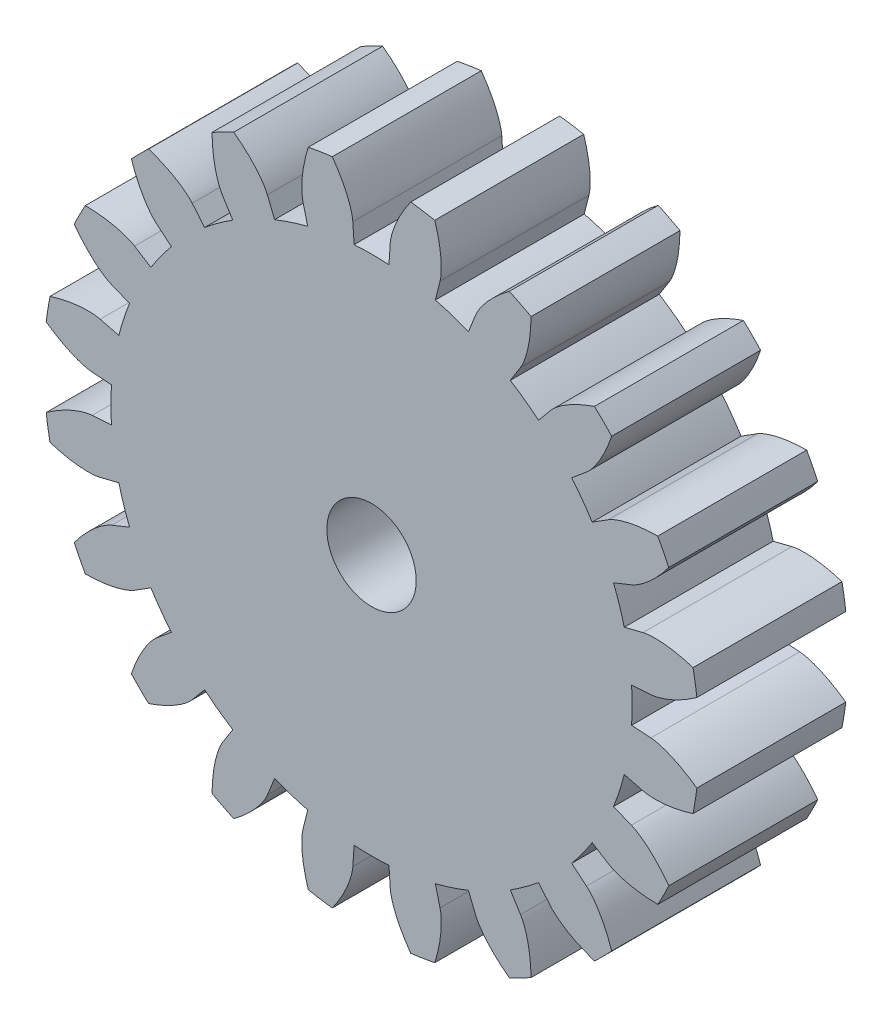
SolidWorks part; units mm, degrees
ref_plane "前视基准面" through (0, 0, 0) normal (0, 0, 1) x (1, 0, 0)
ref_plane "上视基准面" through (0, 0, 0) normal (0, 1, 0) x (1, 0, 0)
ref_plane "右视基准面" through (0, 0, 0) normal (1, 0, 0) x (0, 0, -1)
other "Configuration Table"
sketch "草图1" plane through (0, 0, 0) normal (0, 0, 1) x (1, 0, 0)
  line L0 (0, 0) -> (10, 0) construction
  line L1 (0, 0) -> (9.9692, 0.7846) construction
  line L2 (0, 0) -> (9.3759, 0.6279)
  line L3 (9.9692, 0.7846) -> (9.9692, -0.7846) construction
  line L4 (0, 0) -> (9.3759, -0.6279)
  circle A0 centre (0, 0) radius 11
  circle A1 centre (0, 0) radius 10 construction
  circle A2 centre (0, 0) radius 8.75
  circle A3 centre (0, 0) radius 9.3969 construction
  circle A4 centre (0, 0) radius 1.5
  spline S0 degree 4 poles (9.3759, 0.6279) (9.4116, 0.6303) (9.4826, 0.6384) (9.6794, 0.6787) (10.0428, 0.7996) (10.5707, 1.0588) (11.234, 1.5202) (11.9927, 2.2295) (12.7477, 3.1843) (13.4177, 4.3414) (13.9607, 5.6757) (14.3344, 7.0662) (14.5486, 8.4895) (14.616, 9.9981) (14.5044, 11.8649) (14.0866, 14.0589) (13.234, 16.5111) (11.8775, 19.0558) (10.17, 21.3779) (8.1655, 23.4475) (6.1953, 25.0195) (4.3812, 26.1876) (2.7992, 27.0391) (1.4966, 27.6465) (0.162, 28.1797) (-1.2002, 28.6385) (-2.9309, 29.1192) (-4.693, 29.4765) (-6.2962, 29.6882) (-7.73, 29.7923) (-8.5041, 29.8228) (-8.9819, 29.8324) (-9.3832, 29.8353) (-9.8079, 29.8331) (-10.1583, 29.8266) (-10.8253, 29.8047) (-11.3293, 29.7736) (-11.953, 29.7293) (-12.5015, 29.6752) (-13.0964, 29.6093) (-13.6567, 29.5329) (-14.0975, 29.4672) (-14.3768, 29.4201) (-14.5223, 29.3955) knots 0 0 0 0 0 0.002802 0.005604 0.015718 0.02996 0.048734 0.068727 0.096889 0.125051 0.153212 0.181374 0.209535 0.237696 0.271429 0.327752 0.384075 0.440398 0.496721 0.553044 0.609367 0.637529 0.66569 0.693852 0.722013 0.750174 0.778336 0.834659 0.86282 0.876901 0.890982 0.895509 0.900036 0.909091 0.920455 0.931818 0.943182 0.954545 0.965909 0.977273 0.988636 1 1 1 1 1 construction
  spline S1 degree 4 poles (9.3759, 0.6279) (9.4116, 0.6303) (9.4826, 0.6384) (9.6794, 0.6787) (10.0428, 0.7996) (10.5707, 1.0588) (11.234, 1.5202) (11.9927, 2.2295) (12.7477, 3.1843) (13.4177, 4.3414) (13.9607, 5.6757) (14.3344, 7.0662) (14.5486, 8.4895) (14.616, 9.9981) (14.5044, 11.8649) (14.0866, 14.0589) (13.234, 16.5111) (11.8775, 19.0558) (10.17, 21.3779) (8.1655, 23.4475) (6.1953, 25.0195) (4.3812, 26.1876) (2.7992, 27.0391) (1.4966, 27.6465) (0.162, 28.1797) (-1.2002, 28.6385) (-2.9309, 29.1192) (-4.693, 29.4765) (-6.2962, 29.6882) (-7.73, 29.7923) (-8.5041, 29.8228) (-8.9819, 29.8324) (-9.3832, 29.8353) (-9.6441, 29.834) (-9.8047, 29.8322) (-9.9096, 29.8304) knots 0 0 0 0 0 0.002802 0.005604 0.015718 0.02996 0.048734 0.068727 0.096889 0.125051 0.153212 0.181374 0.209535 0.237696 0.271429 0.327752 0.384075 0.440398 0.496721 0.553044 0.609367 0.637529 0.66569 0.693852 0.722013 0.750174 0.778336 0.834659 0.86282 0.876901 0.890982 0.895509 0.900036 0.909091 0.909091 0.909091 0.909091 0.909091
  spline S2 degree 4 poles (9.3759, -0.6279) (9.4116, -0.6303) (9.4826, -0.6384) (9.6794, -0.6787) (10.0428, -0.7996) (10.5707, -1.0588) (11.234, -1.5202) (11.9927, -2.2295) (12.7477, -3.1843) (13.4177, -4.3414) (13.9607, -5.6757) (14.3344, -7.0662) (14.5486, -8.4895) (14.616, -9.9981) (14.5044, -11.8649) (14.0866, -14.0589) (13.234, -16.5111) (11.8775, -19.0558) (10.17, -21.3779) (8.1655, -23.4475) (6.1953, -25.0195) (4.3812, -26.1876) (2.7992, -27.0391) (1.4966, -27.6465) (0.162, -28.1797) (-1.2002, -28.6385) (-2.9309, -29.1192) (-4.693, -29.4765) (-6.2962, -29.6882) (-7.73, -29.7923) (-8.5041, -29.8228) (-8.9819, -29.8324) (-9.3832, -29.8353) (-9.8079, -29.8331) (-10.1583, -29.8266) (-10.8253, -29.8047) (-11.3293, -29.7736) (-11.953, -29.7293) (-12.5015, -29.6752) (-13.0964, -29.6093) (-13.6567, -29.5329) (-14.0975, -29.4672) (-14.3768, -29.4201) (-14.5223, -29.3955) knots 0 0 0 0 0 0.002802 0.005604 0.015718 0.02996 0.048734 0.068727 0.096889 0.125051 0.153212 0.181374 0.209535 0.237696 0.271429 0.327752 0.384075 0.440398 0.496721 0.553044 0.609367 0.637529 0.66569 0.693852 0.722013 0.750174 0.778336 0.834659 0.86282 0.876901 0.890982 0.895509 0.900036 0.909091 0.920455 0.931818 0.943182 0.954545 0.965909 0.977273 0.988636 1 1 1 1 1 construction
  spline S3 degree 4 poles (9.3759, -0.6279) (9.4116, -0.6303) (9.4826, -0.6384) (9.6794, -0.6787) (10.0428, -0.7996) (10.5707, -1.0588) (11.234, -1.5202) (11.9927, -2.2295) (12.7477, -3.1843) (13.4177, -4.3414) (13.9607, -5.6757) (14.3344, -7.0662) (14.5486, -8.4895) (14.616, -9.9981) (14.5044, -11.8649) (14.0866, -14.0589) (13.234, -16.5111) (11.8775, -19.0558) (10.17, -21.3779) (8.1655, -23.4475) (6.1953, -25.0195) (4.3812, -26.1876) (2.7992, -27.0391) (1.4966, -27.6465) (0.162, -28.1797) (-1.2002, -28.6385) (-2.9309, -29.1192) (-4.693, -29.4765) (-6.2962, -29.6882) (-7.73, -29.7923) (-8.5041, -29.8228) (-8.9819, -29.8324) (-9.3832, -29.8353) (-9.6441, -29.834) (-9.8047, -29.8322) (-9.9096, -29.8304) knots 0 0 0 0 0 0.002802 0.005604 0.015718 0.02996 0.048734 0.068727 0.096889 0.125051 0.153212 0.181374 0.209535 0.237696 0.271429 0.327752 0.384075 0.440398 0.496721 0.553044 0.609367 0.637529 0.66569 0.693852 0.722013 0.750174 0.778336 0.834659 0.86282 0.876901 0.890982 0.895509 0.900036 0.909091 0.909091 0.909091 0.909091 0.909091
  point P15 (9.9692, 0)
  dimension "齿顶圆直径" = 22
  dimension "分度圆直径" = 20
  dimension "齿根圆直径" = 17.5
  dimension "基圆直径" = 18.7939
  dimension "内孔直径" = 3
  dimension "渐近线镜像线夹角" = 4.5
extrude "凸台-拉伸1" add sketch "草图1" along normal blind 5 contours A0 | A4
extrude "切除-拉伸1" cut sketch "草图1<3>" along normal through all contours A2 S3 A0 S1 region at (10.0281, 0, 0)
sketch "草图1<3>" plane through (0, 0, 0) normal (0, 0, 1) x (1, 0, 0) same geometry as "草图1"
pattern_circular "阵列(圆周)1" count 20 every 18 about axis through (0, 0, 5) along (0, 0, 1) of "切除-拉伸1"
equation "\"m\"= 1'模数"
equation "\"z\"= 20'齿数"
equation "\"a\"= 20度'压力角"
equation "\"d\"= \"m\" * \"z\"'分度圆直径"
equation "\"da\"= ( \"z\" + 2 ) * \"m\"'齿顶圆直径"
equation "\"df\"= ( \"z\" - 2.5 ) * \"m\"'齿根圆直径"
equation "\"s\"= 0.5 * PI * \"m\"'分度圆齿厚"
equation "\"r\"= 0.38 * \"m\"'齿根圆角"
equation "\"B\"= 0.3 * \"d\"'齿厚"
equation "\"db\"= \"m\" * \"z\" * cos ( \"a\" )'基圆直径"
equation "\"rb\"= \"db\" / 2'基圆半径"
equation "\"齿顶圆直径@草图1\"= \"da\""
equation "\"分度圆直径@草图1\"= \"d\""
equation "\"齿根圆直径@草图1\"= \"df\""
equation "\"基圆直径@草图1\"= \"db\""
equation "\"渐近线镜像线夹角@草图1\"= 360 / 4 / \"z\""
equation "\"h\"= 5'齿轮厚度"
equation "\"ir\"= 3'内孔直径"
equation "\"内孔直径@草图1\"= \"ir\""
equation "\"齿轮厚@凸台-拉伸1\"= \"h\""
equation "\"齿轮夹角@阵列(圆周)1\"= 360 / \"z\""
equation "\"齿数@阵列(圆周)1\"= \"z\""
